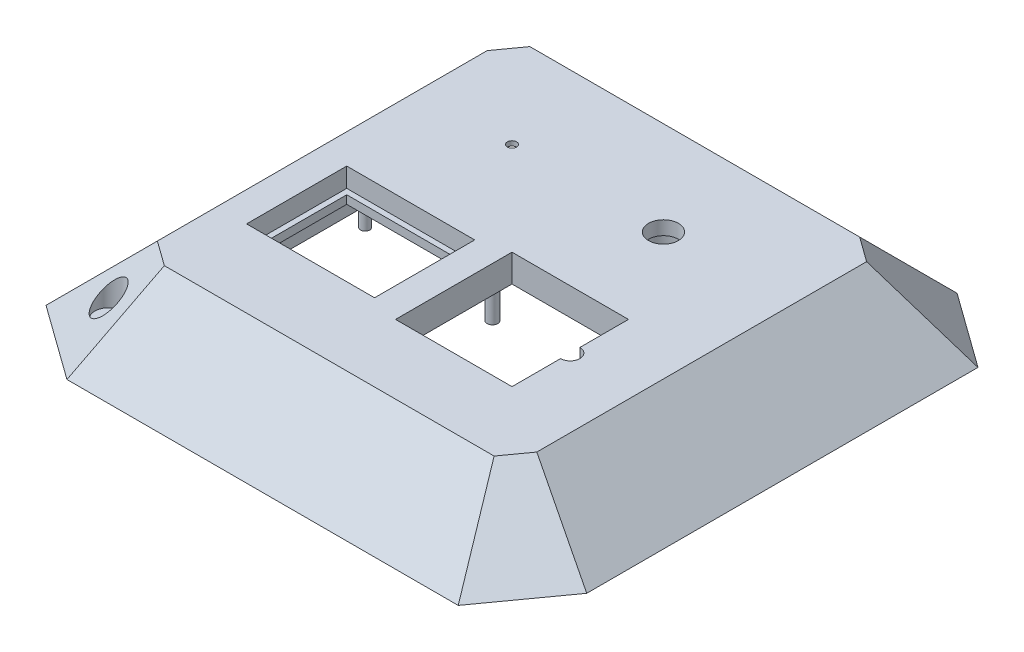
SolidWorks part; units mm, degrees
ref_plane "Front Plane" through (0, 0, 0) normal (0, 0, 1) x (1, 0, 0)
ref_plane "Top Plane" through (0, 0, 0) normal (0, 1, 0) x (1, 0, 0)
ref_plane "Right Plane" through (0, 0, 0) normal (1, 0, 0) x (0, 0, -1)
sketch "Sketch1" plane through (0, 0, 0) normal (0, 1, 0) x (1, 0, 0)
  line L0 (-47.3454, -21.7516) -> (37.6546, -21.7516)
  line L1 (37.6546, -21.7516) -> (49.3368, -5.5181)
  line L2 (49.3368, -5.5181) -> (49.3368, 79.4819)
  line L3 (49.3368, 79.4819) -> (33.1033, 91.1641)
  line L4 (33.1033, 91.1641) -> (-51.8967, 91.1641)
  line L5 (-51.8967, 91.1641) -> (-63.5789, 74.9306)
  line L6 (-63.5789, 74.9306) -> (-63.5789, -10.0694)
  line L7 (-63.5789, -10.0694) -> (-47.3454, -21.7516)
  dimension "D2" = 85
  dimension "D3" = 85
  dimension "D4" = 144.26
  dimension "D5" = 144.26
  dimension "D6" = 85
  dimension "D7" = 144.26
  dimension "D8" = 20
  dimension "D9" = 85
  dimension "D10" = 20
  dimension "D11" = 20
extrude "Boss-Extrude2" add sketch "Sketch1" along normal blind 16
sketch "Sketch4" plane through (0, 0, 0) normal (0, -1, 0) x (1, 0, 0)
  line L16 (-42.1868, 5.7516) -> (-47.5789, 1.8712)
  line L17 (-47.5789, 1.8712) -> (-47.5789, -69.772)
  line L18 (-47.5789, -69.772) -> (-43.6985, -75.1641)
  line L19 (-43.6985, -75.1641) -> (27.9447, -75.1641)
  line L20 (27.9447, -75.1641) -> (33.3368, -71.2838)
  line L21 (33.3368, -71.2838) -> (33.3368, 0.3594)
  line L22 (33.3368, 0.3594) -> (29.4564, 5.7516)
  line L23 (29.4564, 5.7516) -> (-42.1868, 5.7516)
  line L24 (-42.1868, 5.7516) -> (-47.5789, 1.8712)
  line L25 (-47.5789, 1.8712) -> (-47.5789, -69.772)
  line L26 (-47.5789, -69.772) -> (-43.6985, -75.1641)
  line L27 (-43.6985, -75.1641) -> (27.9447, -75.1641)
  line L28 (27.9447, -75.1641) -> (33.3368, -71.2838)
  line L29 (33.3368, -71.2838) -> (33.3368, 0.3594)
  line L30 (33.3368, 0.3594) -> (29.4564, 5.7516)
  line L31 (29.4564, 5.7516) -> (-42.1868, 5.7516)
  dimension "D1" = 16
chamfer "Chamfer1" distance 16 angle 45 8 edges at (-63.5789, 16, -32.4306) (-57.7378, 16, -83.0473) (-9.3967, 16, -91.1641) (41.22, 16, -85.323) (49.3368, 16, -36.9819) (43.4957, 16, 13.6348) (-4.8454, 16, 21.7516) (-55.4621, 16, 15.9105)
extrude "Cut-Extrude3" cut sketch "Sketch4" against normal blind 10
sketch "Sketch6" plane through (0, 16, 0) normal (0, 1, 0) x (1, 0, 0)
  line L0 (33.3368, -0.3594) -> (33.3368, 71.2838) construction
  line L1 (-6.9632, 34.5484) -> (18.3368, 34.5484)
  line L2 (-6.9632, 34.5484) -> (-6.9632, 9.2484)
  line L3 (-6.9632, 9.2484) -> (18.3368, 9.2484)
  line L4 (18.3368, 34.5484) -> (18.3368, 9.2484)
  line L5 (-42.1868, -5.7516) -> (29.4564, -5.7516) construction
  dimension "D1" = 25.3
  dimension "D2" = 25.3
  dimension "D3" = 15
  dimension "D4" = 15
extrude "Cut-Extrude4" cut sketch "Sketch6" against normal up to next
sketch "Sketch7" plane through (0, 10, 0) normal (0, -1, 0) x (1, 0, 0)
  line L0 (18.3368, -9.2484) -> (18.3368, -34.5484) construction
  circle A0 centre (18.3368, -21.8984) radius 2.0981
extrude "Cut-Extrude5" cut sketch "Sketch7" against normal up to next
sketch "Sketch8" plane through (0, 10, 0) normal (0, -1, 0) x (1, 0, 0)
  line L0 (-11.7632, -21.9984) -> (30.1662, -21.9984) construction
  line L1 (-11.7632, -8.8984) -> (24.2368, -8.8984)
  line L2 (-11.7632, -8.8984) -> (-11.7632, -35.0984)
  line L3 (-11.7632, -35.0984) -> (24.2368, -35.0984)
  line L4 (24.2368, -8.8984) -> (24.2368, -35.0984)
  line L5 (6.2368, -8.8984) -> (6.2368, -38.2867) construction
  line L6 (33.3368, -71.2838) -> (33.3368, 0.3594) construction
  line L7 (29.4564, 5.7516) -> (-42.1868, 5.7516) construction
  circle A0 centre (-9.2132, -11.4484) radius 1.15
  circle A1 centre (21.6868, -11.4484) radius 1.15
  circle A2 centre (21.6868, -32.5484) radius 1.15
  circle A3 centre (-9.2132, -32.5484) radius 1.15
  dimension "D3" = 2.3
  dimension "D4" = 2.55
  dimension "D5" = 2.55
  dimension "D6" = 9.1
  dimension "D1" = 36
  dimension "D2" = 26.2
  dimension "D7" = 14.65
extrude "Boss-Extrude3" add sketch "Sketch8" along normal blind 7 contours A0 | A1 | A2 | A3 region at (-9.2132, 10, -11.4484) region at (21.6868, 10, -11.4484) region at (21.6868, 10, -32.5484)
sketch "Sketch9" plane through (0, 10, 0) normal (0, -1, 0) x (1, 0, 0)
  line L2 (-47.5789, 1.8712) -> (-47.5789, -69.772) construction
  line L3 (-43.6985, -75.1641) -> (27.9447, -75.1641) construction
  circle A0 centre (-27.2189, -54.8041) radius 15.65
  dimension "D1" = 20.36
  dimension "D2" = 20.36
  dimension "D3" = 31.3
extrude "Cut-Extrude6" cut sketch "Sketch9" against normal blind 5
sketch "Sketch10" plane through (0, 15, 0) normal (0, -1, 0) x (1, 0, 0)
  circle A0 centre (-27.2189, -54.8041) radius 1
  dimension "D1" = 2
extrude "Cut-Extrude7" cut sketch "Sketch10" against normal up to next
sketch "Sketch11" plane through (0, 16, 0) normal (0, 1, 0) x (1, 0, 0)
  line L0 (-14.7144, 21.8984) -> (-6.9632, 21.8984) construction
  line L1 (-14.7144, 35.3984) -> (-39.7144, 35.3984)
  line L2 (-14.7144, 35.3984) -> (-14.7144, 8.3984)
  line L3 (-14.7144, 8.3984) -> (-39.7144, 8.3984)
  line L4 (-39.7144, 35.3984) -> (-39.7144, 8.3984)
  line L5 (-6.9632, 34.5484) -> (-6.9632, 9.2484) construction
  line L6 (-27.2144, 35.3984) -> (-27.2144, 2.0931) construction
  line L7 (-14.7144, 21.8984) -> (-44.3409, 21.8984) construction
  circle A0 centre (-37.5644, 33.2484) radius 1
  circle A1 centre (-16.8644, 33.2484) radius 1
  circle A2 centre (-16.8644, 10.5484) radius 1
  circle A3 centre (-37.5644, 10.5484) radius 1
  dimension "D3" = 2
  dimension "D4" = 2.15
  dimension "D5" = 2.15
  dimension "D1" = 25
  dimension "D2" = 27
extrude "Boss-Extrude4" add sketch "Sketch11" against normal blind 10 contours A0 | A1 | A2 | A3
sketch "Sketch12" plane through (0, 16, 0) normal (0, 1, 0) x (1, 0, 0)
  line L0 (-14.7144, 35.3984) -> (-14.7144, 8.3984) construction
  line L1 (-39.9144, 31.5984) -> (-14.5144, 31.5984)
  line L2 (-39.9144, 31.5984) -> (-39.9144, 12.2384)
  line L3 (-39.9144, 12.2384) -> (-14.5144, 12.2384)
  line L4 (-14.5144, 31.5984) -> (-14.5144, 12.2384)
  line L5 (-39.7144, 35.3984) -> (-39.7144, 8.3984) construction
  line L6 (-14.7144, 35.3984) -> (-39.7144, 35.3984) construction
  line L7 (-14.7144, 8.3984) -> (-39.7144, 8.3984) construction
  dimension "D1" = 0.2
  dimension "D2" = 0.2
  dimension "D3" = 3.8
  dimension "D4" = 3.84
extrude "Cut-Extrude8" cut sketch "Sketch12" against normal through all
sketch "Sketch13" plane through (0, 16, 0) normal (0, 1, 0) x (1, 0, 0)
  line L0 (-14.5144, 31.5984) -> (-39.9144, 31.5984) construction
  line L1 (-41.1144, 32.7984) -> (-13.3144, 32.7984)
  line L2 (-41.1144, 32.7984) -> (-41.1144, 11.0384)
  line L3 (-41.1144, 11.0384) -> (-13.3144, 11.0384)
  line L4 (-13.3144, 32.7984) -> (-13.3144, 11.0384)
  line L5 (-39.9144, 31.5984) -> (-39.9144, 12.2384) construction
  line L6 (-14.5144, 12.2384) -> (-14.5144, 31.5984) construction
  line L7 (-39.9144, 12.2384) -> (-14.5144, 12.2384) construction
  dimension "D1" = 1.2
  dimension "D2" = 1.2
  dimension "D3" = 1.2
  dimension "D4" = 1.2
extrude "Cut-Extrude9" cut sketch "Sketch13" against normal blind 4.2
sketch "Sketch14" plane through (0, 16, 0) normal (0, 1, 0) x (1, 0, 0)
  line L0 (5.6868, 54.8041) -> (-27.2189, 54.8041) construction
  line L1 (5.6868, 54.8041) -> (5.6868, 34.5484) construction
  line L2 (18.3368, 34.5484) -> (-6.9632, 34.5484) construction
  circle A0 centre (5.6868, 54.8041) radius 3.25
  dimension "D1" = 6.5
extrude "Cut-Extrude10" cut sketch "Sketch14" against normal through all
sketch "Sketch15" plane through (0, 10, 0) normal (0, -1, 0) x (1, 0, 0)
  circle A0 centre (5.6868, -54.8041) radius 4.25
  dimension "D1" = 8.5
extrude "Cut-Extrude11" cut sketch "Sketch15" against normal blind 3
sketch "Sketch17" plane through (0, 16, 0) normal (0, 1, 0) x (1, 0, 0)
  line L0 (-47.5789, -1.8712) -> (-42.1868, -5.7516) construction
  circle A0 centre (-50.1868, -9.8507) radius 3
  circle A1 centre (-50.1868, -9.8507) radius 1.25
  dimension "D1" = 6
  dimension "D2" = 8
  dimension "D4" = 2.5
  dimension "D3" = 8
extrude "Cut-Extrude12" cut sketch "Sketch17" against normal through all contours A1
extrude "Cut-Extrude13" cut sketch "Sketch17<4>" against normal blind 12 contours A0
sketch "Sketch17<4>" plane through (0, 16, 0) normal (0, 1, 0) x (1, 0, 0) same geometry as "Sketch17"
